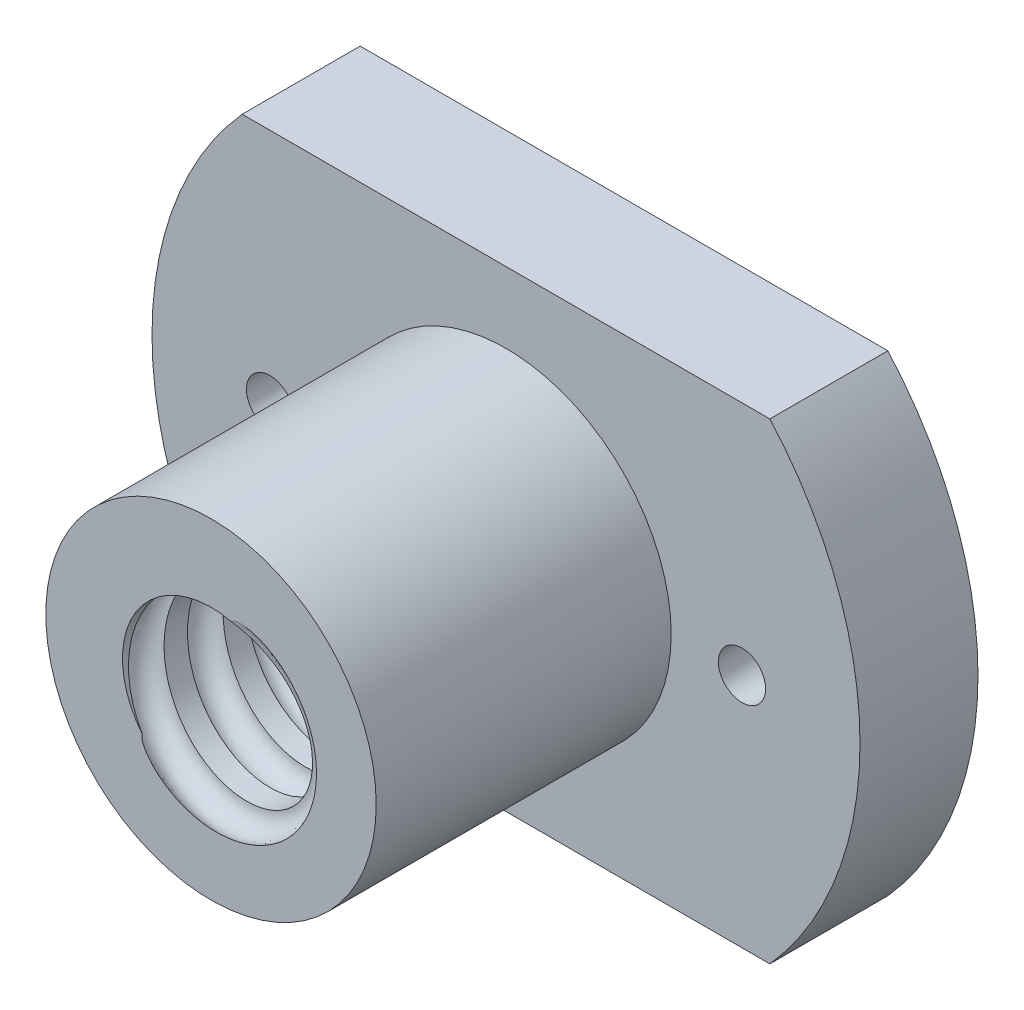
SolidWorks part; units mm, degrees
ref_plane "Front Plane" through (0, 0, 0) normal (0, 0, 1) x (1, 0, 0)
ref_plane "Top Plane" through (0, 0, 0) normal (0, 1, 0) x (1, 0, 0)
ref_plane "Right Plane" through (0, 0, 0) normal (1, 0, 0) x (0, 0, -1)
sketch "Sketch1" plane through (0, 0, 0) normal (0, 0, 1) x (1, 0, 0)
  circle A0 centre (0, 0) radius 7.5
  circle A1 centre (0, 0) radius 14
  dimension "D1" = 15
  dimension "D2" = 28
extrude "Boss-Extrude1" add sketch "Sketch1" against normal blind 35
sketch "Sketch2" plane through (0, 0, -35) normal (0, 0, -1) x (-1, 0, 0)
  circle A0 centre (0, 0) radius 6.75
curve "Helix/Spiral1" pitch 5 height 50 turns 10
ref_plane "Plane1" through (5.7243, -3.577, -35) normal (0.5263, 0.8422, 0.1171) x (0.8503, -0.5213, -0.0725)
sketch "Sketch3" plane through (5.7243, -3.577, -35) normal (0.5263, 0.8422, 0.1171) x (0.8503, -0.5213, -0.0725)
  circle A0 centre (0.748, -0.0547) radius 1.5
  dimension "D1" = 3
sweep "Cut-Sweep1" cut profiles "Sketch3" path "Helix/Spiral1" align with end faces yes
sketch "Sketch4" plane through (0, 0, -35) normal (0, 0, -1) x (-1, 0, 0)
  line L4 (0, 20) -> (2.4691, 20)
  line L5 (22.3607, 20) -> (-22.3607, 20)
  line L7 (-22.3607, -20) -> (22.3607, -20)
  arc A0 (-22.3607, 20) -> (-22.3607, -20) centre (0, 0) ccw
  arc A1 (22.3607, -20) -> (22.3607, 20) centre (0, 0) ccw
  circle A2 centre (0, 0) radius 14
  dimension "D1" = 60
extrude "Boss-Extrude2" add sketch "Sketch4" against normal blind 10 contours L5 A0 L7 A1 | A2
sketch "Sketch5" plane through (0, 0, -35) normal (0, 0, -1) x (-1, 0, 0)
  circle A0 centre (0, 0) radius 20
  circle A1 centre (20, 0) radius 2
  circle A2 centre (-20, 0) radius 2
  dimension "D1" = 40
  dimension "D2" = 4
  dimension "D3" = 4
extrude "Cut-Extrude1" cut sketch "Sketch5" against normal blind 32 contours A0 A2 | A0 A2 | A0 A1 | A0 A1
